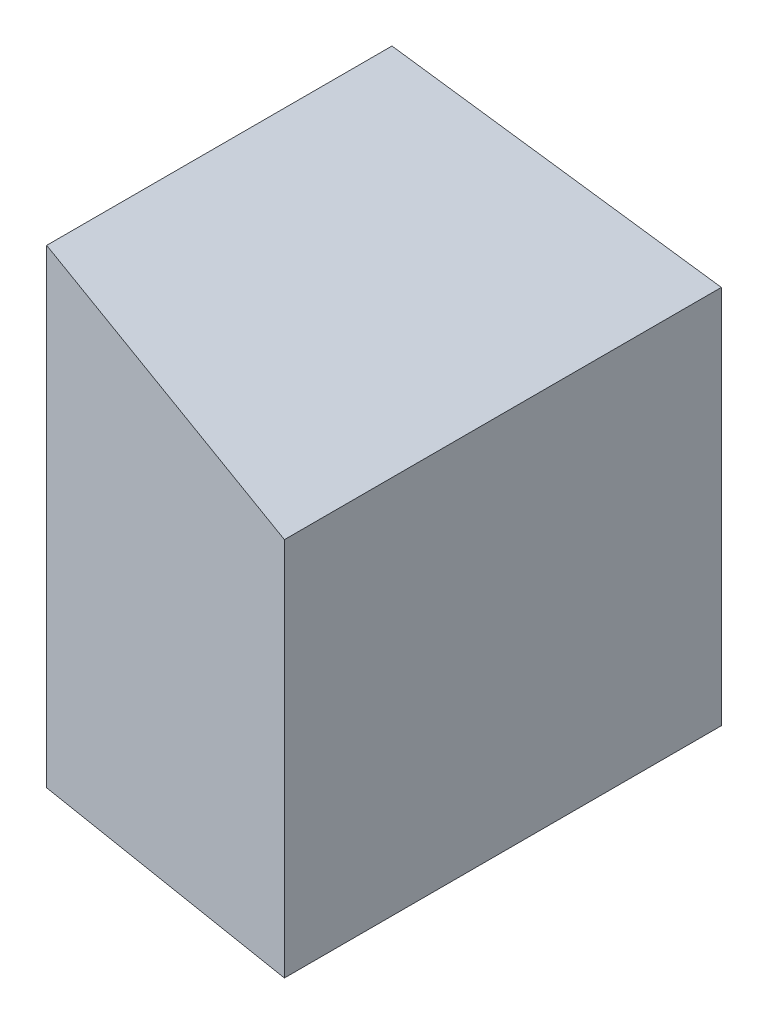
SolidWorks part; units mm, degrees
ref_plane "Front Plane" through (0, 0, 0) normal (0, 0, 1) x (1, 0, 0)
ref_plane "Top Plane" through (0, 0, 0) normal (0, 1, 0) x (1, 0, 0)
ref_plane "Right Plane" through (0, 0, 0) normal (1, 0, 0) x (0, 0, -1)
sketch "Sketch1" plane through (0, 0, 0) normal (0, 0, 1) x (1, 0, 0)
  line L0 (0, 0) -> (1349, 0)
  line L1 (1349, 1806) -> (1349, 0)
  line L2 (1349, 1806) -> (0, 2235)
  line L3 (0, 2235) -> (0, 0)
  point P3 (0, 0)
  point P5 (0, 0)
  dimension "D1" = 1349
  dimension "D2" = 2235
  dimension "D3" = 1806
extrude "Boss-Extrude1" add sketch "Sketch1" along normal blind 1039.25 and the other way blind 1039.25
sketch "Sketch2" plane through (0, 0, 0) normal (0, -1, 0) x (1, 0, 0)
  line L0 (0, 821.33) -> (0, 1039.25)
  line L1 (0, -1039.25) -> (0, 1039.25) construction
  line L2 (0, 1039.25) -> (1349, 1039.25)
  line L3 (1349, 1039.25) -> (0, 821.33)
  line L4 (0, 0) -> (-1860.8429, 0) construction
  line L5 (0, -1039.25) -> (1349, -1039.25)
  line L6 (0, -821.33) -> (0, -1039.25)
  line L7 (1349, -1039.25) -> (0, -821.33)
  dimension "D1" = 217.92
extrude "Cut-Extrude1" cut sketch "Sketch2" against normal blind 4942.25
